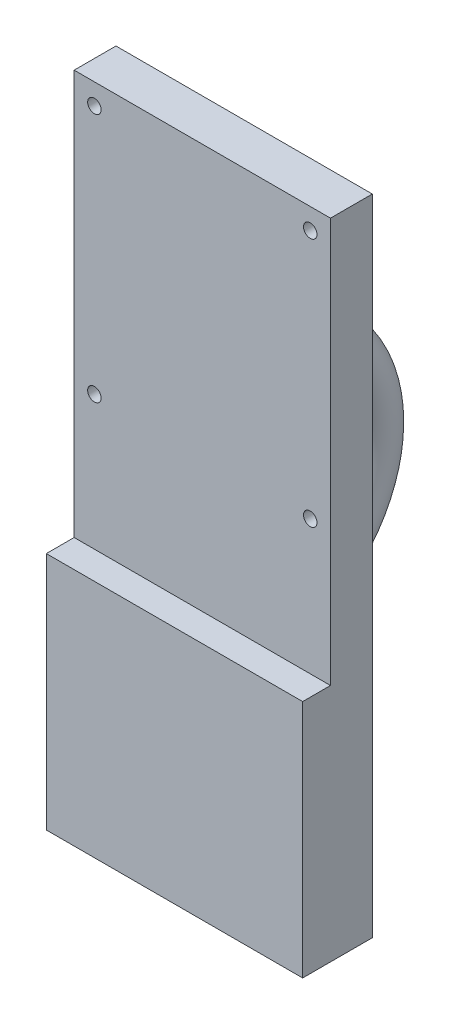
SolidWorks part; units mm, degrees
ref_plane "Plan de face" through (0, 0, 0) normal (0, 0, 1) x (1, 0, 0)
ref_plane "Plan de dessus" through (0, 0, 0) normal (0, 1, 0) x (1, 0, 0)
ref_plane "Plan de droite" through (0, 0, 0) normal (1, 0, 0) x (0, 0, -1)
sketch "Esquisse1" plane through (0, 0, 0) normal (0, 0, 1) x (1, 0, 0)
  line L1 (0, 0) -> (190, 0)
  line L2 (0, 0) -> (0, 300)
  line L3 (0, 300) -> (190, 300)
  line L4 (190, 0) -> (190, 300)
  dimension "D1" = 190
  dimension "D2" = 300
extrude "Boss.-Extru.1" add sketch "Esquisse1" along normal blind 31
sketch "Esquisse2" plane through (0, 0, 0) normal (0, 0, -1) x (-1, 0, 0)
  line L0 (-190, 300) -> (0, 300) construction
  line L3 (-190, 0) -> (-190, 300) construction
  line L4 (0, 300) -> (0, 0) construction
  line L5 (-1232.0432, 99.5) -> (48767.9568, 99.5) construction
  circle A0 centre (-175, 284.5) radius 5
  circle A1 centre (-15, 284.5) radius 5
  circle A2 centre (-175, 99.5) radius 5
  circle A3 centre (-15, 99.5) radius 5
  dimension "D1" = 10
  dimension "D4" = 10
  dimension "D8" = 10
  dimension "D9" = 10
  dimension "D2" = 15.5
  dimension "D3" = 15
  dimension "D5" = 15
  dimension "D6" = 15.5
  dimension "D7" = 200.5
  dimension "D10" = 15
  dimension "D11" = 15
extrude "Enlèv. mat.-Extru.1" cut sketch "Esquisse2" against normal through all
sketch "Esquisse3" plane through (0, 0, 0) normal (0, -1, 0) x (1, 0, 0)
  line L1 (0, 0) -> (190, 0)
  line L2 (0, 0) -> (0, 51.62)
  line L3 (0, 51.62) -> (190, 51.62)
  line L4 (190, 0) -> (190, 51.62)
  dimension "D1" = 190
  dimension "D2" = 51.62
extrude "Boss.-Extru.2" add sketch "Esquisse3" along normal blind 177.45
sketch "Esquisse4" plane through (0, 0, 0) normal (0, 0, -1) x (-1, 0, 0)
  line L0 (-190, -177.45) -> (0, 300) construction
  line L1 (-190, 300) -> (0, -177.45) construction
  line L2 (-1095, 61.275) -> (48905, 61.275) construction
  line L3 (-95, -938.725) -> (-95, 49061.275) construction
  circle A0 centre (-95, -28.725) radius 20
  point P11 (-95, 61.275)
  dimension "D1" = 40
  dimension "D2" = 90
revolve "Révolution1" add sketch "Esquisse4" angle 180 about L2 reverse direction yes
equation "\"D7@Esquisse2\"=216-15.5"
equation "\"D2@Esquisse3\"=31+20.62"
